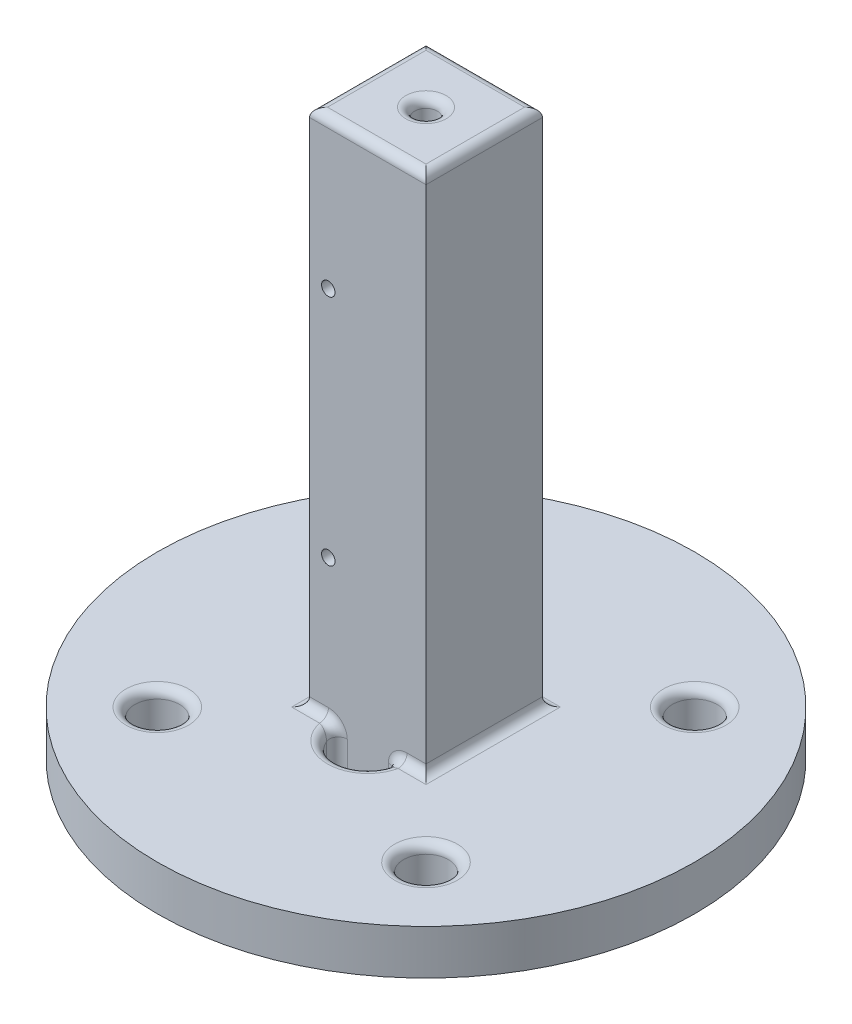
SolidWorks part; units mm, degrees
ref_plane "Front Plane" through (0, 0, 0) normal (0, 0, 1) x (1, 0, 0)
ref_plane "Top Plane" through (0, 0, 0) normal (0, 1, 0) x (1, 0, 0)
ref_plane "Right Plane" through (0, 0, 0) normal (1, 0, 0) x (0, 0, -1)
sketch "Sketch1" plane through (0, 0, 0) normal (0, 1, 0) x (1, 0, 0)
  circle A0 centre (0, 0) radius 30
  dimension "D1" = 60
extrude "Boss-Extrude1" add sketch "Sketch1" along normal blind 5
sketch "Sketch2" plane through (0, 5, 0) normal (0, 1, 0) x (1, 0, 0)
  line L1 (-6.5, 6.5) -> (6.5, 6.5)
  line L2 (-6.5, 6.5) -> (-6.5, -6.5)
  line L3 (-6.5, -6.5) -> (6.5, -6.5)
  line L4 (6.5, 6.5) -> (6.5, -6.5)
  line L5 (-6.5, 6.5) -> (6.5, -6.5) construction
  line L6 (-6.5, -6.5) -> (6.5, 6.5) construction
  point P0 (0, 0)
  dimension "D1" = 13
extrude "Boss-Extrude2" add sketch "Sketch2" along normal blind 58
sketch "Sketch3" plane through (0, 63, 0) normal (0, 1, 0) x (1, 0, 0)
  circle A0 centre (0, 0) radius 1.25
  dimension "D1" = 2.5
extrude "Cut-Extrude1" cut sketch "Sketch3" against normal blind 15
sketch "Sketch4" plane through (0, 5, 0) normal (0, 1, 0) x (1, 0, 0)
  line L0 (-3.5, -6.5) -> (3.5, -6.5)
  line L1 (-15, 15) -> (15, 15) construction
  line L2 (-15, 15) -> (-15, -15) construction
  line L3 (-15, -15) -> (15, -15) construction
  line L4 (15, 15) -> (15, -15) construction
  line L5 (-15, 15) -> (15, -15) construction
  line L6 (-15, -15) -> (15, 15) construction
  line L7 (-6.5, -6.5) -> (6.5, -6.5) construction
  circle A0 centre (-15, 15) radius 2.5
  circle A1 centre (15, 15) radius 2.5
  circle A2 centre (15, -15) radius 2.5
  circle A3 centre (-15, -15) radius 2.5
  circle A4 centre (0, -6.5) radius 3.5
  point P0 (0, 0)
  point P15 (0, -6.5)
  line M9 (6.5, -6.5) -> (-6.5, -6.5)
  dimension "D2" = 5
  dimension "D1" = 30
  dimension "D3" = 7
extrude "Cut-Extrude2" cut sketch "Sketch4" against normal up to surface (5 mm away) contours A4 M9 | A2 | A3 | A0 | A1 region at (0, 5, 7.9854) region at (-15, 5, -15) region at (15, 5, -15) region at (15, 5, 15) region at (-15, 5, 15) up to face at (0, 0, 30)
fillet "Fillet1" radius 1 1 edges at (0, 5, 10)
fillet "Fillet2" radius 1 18 edges at (3.5, 2, 6.5) (3.7929, 4.7071, 6.5) (-3.5, 2, 6.5) (-3.7929, 4.7071, 6.5) (-15, 5, -12.5) (-15, 5, 17.5) (15, 5, 17.5) (15, 5, -12.5) (0, 5, -6.5) (-6.5, 5, 0) (5.5, 5, 6.5) (-5.5, 5, 6.5) (6.5, 5, 0) (0, 63, 1.25) (6.5, 63, 0) (0, 63, -6.5) (-6.5, 63, 0) (0, 63, 6.5)
sketch "Sketch5" plane through (0, 0, 6.5) normal (0, 0, 1) x (1, 0, 0)
  line L0 (-4.41, 62) -> (-4.41, 46.5) construction
  line L1 (6.5, 62) -> (-6.5, 62) construction
  line L2 (-6.5, 62) -> (-6.5, 6) construction
  line L3 (-4.41, 46.5) -> (-4.41, 20.5) construction
  circle A0 centre (-4.41, 46.5) radius 0.75
  circle A1 centre (-4.41, 20.5) radius 0.75
  dimension "D4" = 1.5
  dimension "D1" = 2.09
  dimension "D2" = 15.5
  dimension "D3" = 26
extrude "Cut-Extrude3" cut sketch "Sketch5" against normal up to surface (13 mm away) up to face at (0, 34, -6.5)
